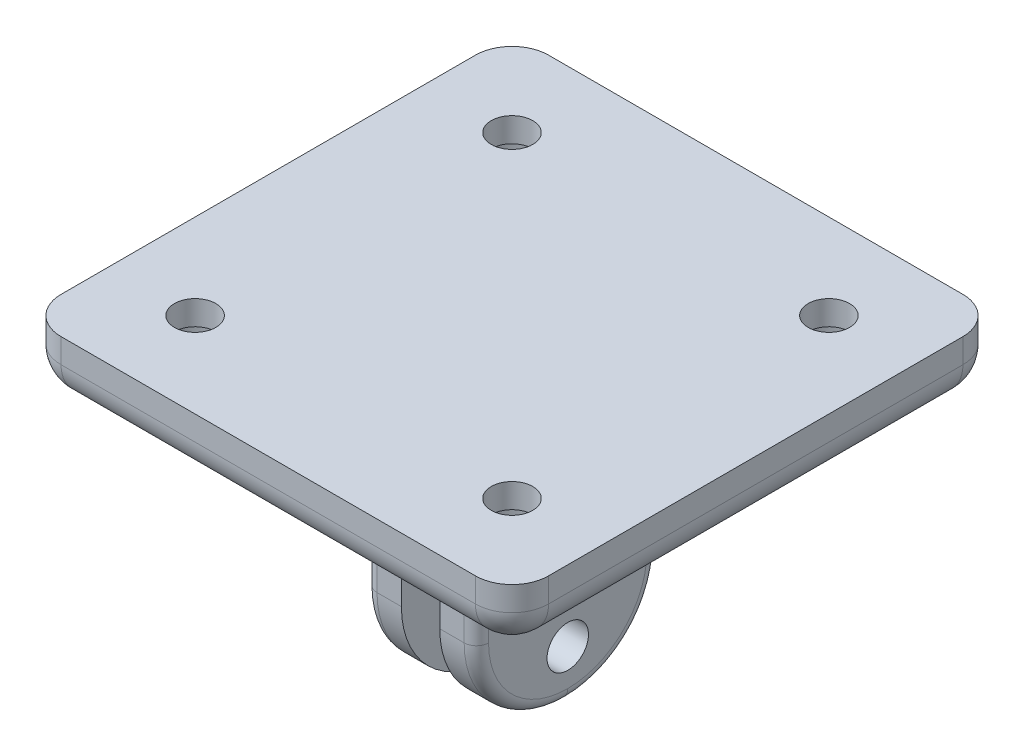
SolidWorks part; units mm, degrees
ref_plane "Front Plane" through (0, 0, 0) normal (0, 0, 1) x (1, 0, 0)
ref_plane "Top Plane" through (0, 0, 0) normal (0, 1, 0) x (1, 0, 0)
ref_plane "Right Plane" through (0, 0, 0) normal (1, 0, 0) x (0, 0, -1)
sketch "Sketch1" plane through (0, 0, 0) normal (0, 1, 0) x (1, 0, 0)
  line L0 (-3.075, 0) -> (3.075, 0) construction
  line L2 (-1.575, -7.5) -> (-4.575, -7.5)
  line L3 (-1.575, -7.5) -> (-1.575, 7.5)
  line L4 (-1.575, 7.5) -> (-4.575, 7.5)
  line L5 (-4.575, -7.5) -> (-4.575, 7.5)
  line L6 (-1.575, -7.5) -> (-4.575, 7.5) construction
  line L7 (-1.575, 7.5) -> (-4.575, -7.5) construction
  line L8 (4.575, -7.5) -> (1.575, -7.5)
  line L9 (4.575, -7.5) -> (4.575, 7.5)
  line L10 (4.575, 7.5) -> (1.575, 7.5)
  line L11 (1.575, -7.5) -> (1.575, 7.5)
  line L12 (4.575, -7.5) -> (1.575, 7.5) construction
  line L13 (4.575, 7.5) -> (1.575, -7.5) construction
  point P4 (0, 0)
  dimension "D1" = 3.15
  dimension "D2" = 3
  dimension "D3" = 15
extrude "Boss-Extrude1" add sketch "Sketch1" along normal blind 20.225
sketch "Sketch2" plane through (0, 20.225, 0) normal (0, 1, 0) x (1, 0, 0)
  line L1 (20, -20) -> (-20, -20)
  line L2 (20, -20) -> (20, 20)
  line L3 (20, 20) -> (-20, 20)
  line L4 (-20, -20) -> (-20, 20)
  line L5 (20, -20) -> (-20, 20) construction
  line L6 (20, 20) -> (-20, -20) construction
  point P0 (0, 0)
  dimension "D2" = 40
extrude "Boss-Extrude2" add sketch "Sketch2" along normal blind 5
sketch "Sketch3" plane through (-4.575, 0, 0) normal (-1, 0, 0) x (0, 0, 1)
  line L0 (0, 0) -> (0, 4) construction
  line L1 (-7.5, 0) -> (7.5, 0) construction
  line L2 (0, 4) -> (0, 11) construction
  point P7 (0, 11)
  point P8 (0, 4)
  dimension "D1" = 4
  dimension "D2" = 7
hole_wizard "M3 Clearance Hole1" positions "Sketch4" profile "Sketch5" hole size "M3" standard "ANSI Metric" end condition through all
sketch "Sketch4" plane through (-4.575, 0, 0) normal (-1, 0, 0) x (0, 0, 1)
  point P0 (0, 11)
  point P3 (0, 4)
sketch "Sketch5" plane through (-4.575, 11, 0) normal (0, 1, 0) x (0, 0, 1)
  line L0 (0, 0) -> (0, 24.575)
  line L1 (0, 24.575) -> (1.7, 24.575)
  line L2 (1.7, 24.575) -> (1.7, 0)
  line L5 (1.7, 0) -> (0, 0)
  line L11 (0, -6.35) -> (0, 107.95) construction
  dimension "Thru Hole Dia." = 3.4
  dimension "Thru Hole Depth" = 24.575
fillet "Fillet1" radius 7.5 4 edges at (3.075, 0, 7.5) (-3.075, 0, 7.5) (-3.075, 0, -7.5) (3.075, 0, -7.5)
fillet "Fillet3" radius 1 14 edges at (4.575, 13.8625, -7.5) (4.575, 2.1967, -5.3033) (4.575, 2.1967, 5.3033) (-4.575, 13.8625, -7.5) (-4.575, 2.1967, -5.3033) (-4.575, 2.1967, 5.3033) (4.575, 13.8625, 7.5) (-4.575, 13.8625, 7.5) (3.075, 20.225, -7.5) (-3.075, 20.225, -7.5) (3.075, 20.225, 7.5) (-3.075, 20.225, 7.5) (4.575, 20.225, 0) (-4.575, 20.225, 0)
sketch "Sketch6" plane through (0, 20.225, 0) normal (0, -1, 0) x (1, 0, 0)
  line L0 (-20, 20) -> (20, 20) construction
  line L1 (-13, -13) -> (13, -13) construction
  line L2 (-13, -13) -> (-13, 13) construction
  line L3 (-13, 13) -> (13, 13) construction
  line L4 (13, -13) -> (13, 13) construction
  line L5 (-13, -13) -> (13, 13) construction
  line L6 (-13, 13) -> (13, -13) construction
  point P0 (0, 0)
  point P9 (13, 13)
  point P10 (13, -13)
  point P11 (-13, -13)
  point P12 (-13, 13)
  dimension "D1" = 7
hole_wizard "CBORE for M3 SHCS1" positions "Sketch7" profile "Sketch8" counterbore size "M3" standard "ANSI Metric" end condition up to next
sketch "Sketch7" plane through (0, 20.225, 0) normal (0, -1, 0) x (-1, 0, 0)
  point P0 (-13, -13)
  point P3 (-13, 13)
  point P6 (13, 13)
  point P9 (13, -13)
sketch "Sketch8" plane through (13, 20.225, 13) normal (1, 0, 0) x (0, 0, -1)
  line L0 (0, 0) -> (0, 5)
  line L1 (0, 5) -> (1.7, 5)
  line L3 (1.7, 5) -> (1.7, 3)
  line L4 (1.7, 3) -> (3.25, 3)
  line L5 (3.25, 3) -> (3.25, 0)
  line L7 (3.25, 0) -> (0, 0)
  line L11 (0, -6.35) -> (0, 107.95) construction
  dimension "Thru Hole Dia." = 3.4
  dimension "Thru Hole Depth" = 5
  dimension "C'Bore Dia." = 6.5
  dimension "C'Bore Depth" = 3
fillet "Fillet5" radius 3 8 edges at (-20, 22.725, 20) (-20, 22.725, -20) (20, 22.725, -20) (20, 22.725, 20) (-20, 20.225, 0) (0, 20.225, 20) (20, 20.225, 0) (0, 20.225, -20)
